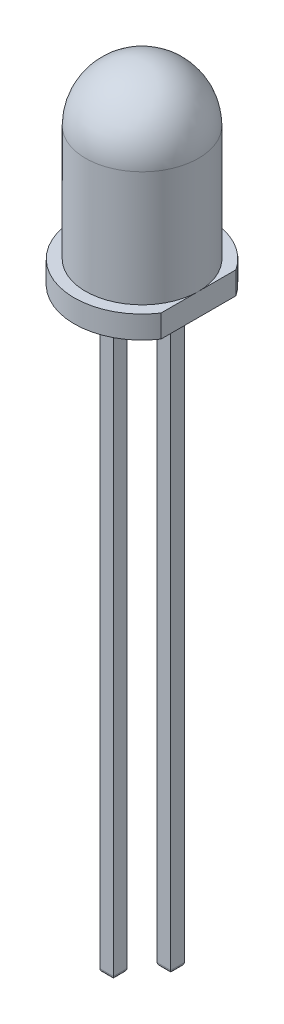
SolidWorks part; units mm, degrees
ref_plane "Front Plane" through (0, 0, 0) normal (0, 0, 1) x (1, 0, 0)
ref_plane "Top Plane" through (0, 0, 0) normal (0, 1, 0) x (1, 0, 0)
ref_plane "Right Plane" through (0, 0, 0) normal (1, 0, 0) x (0, 0, -1)
sketch "Sketch1" plane through (0, 0, 0) normal (0, 1, 0) x (1, 0, 0)
  circle A0 centre (0, 0) radius 2.5
  dimension "D1" = 5
extrude "Boss-Extrude1" add sketch "Sketch1" along normal mid plane 8.6
sketch "Sketch2" plane through (0, -4.3, 0) normal (0, -1, 0) x (1, 0, 0)
  circle A0 centre (0, 0) radius 3
  dimension "D1" = 6
extrude "Boss-Extrude2" add sketch "Sketch2" against normal blind 1
fillet "Fillet1" radius 2.5 1 edges at (0, 4.3, 2.5)
sketch "Sketch3" plane through (0, 0, 0) normal (0, 0, 1) x (1, 0, 0)
  line L1 (2.5, -3.3) -> (3.4542, -3.3)
  line L2 (2.5, -3.3) -> (2.5, -4.7256)
  line L3 (2.5, -4.7256) -> (3.4542, -4.7256)
  line L4 (3.4542, -3.3) -> (3.4542, -4.7256)
extrude "Cut-Extrude1" cut sketch "Sketch3" against normal through all both and the other way through all
sketch "Sketch4" plane through (0, -4.3, 0) normal (0, -1, 0) x (1, 0, 0)
  line L1 (-0.97, -0.3) -> (-1.57, -0.3)
  line L2 (-0.97, -0.3) -> (-0.97, 0.3)
  line L3 (-0.97, 0.3) -> (-1.57, 0.3)
  line L4 (-1.57, -0.3) -> (-1.57, 0.3)
  line L5 (-0.97, -0.3) -> (-1.57, 0.3) construction
  line L6 (-0.97, 0.3) -> (-1.57, -0.3) construction
  line L7 (0.97, 0.3) -> (1.57, 0.3)
  line L8 (0.97, 0.3) -> (0.97, -0.3)
  line L9 (0.97, -0.3) -> (1.57, -0.3)
  line L10 (1.57, 0.3) -> (1.57, -0.3)
  line L11 (0.97, 0.3) -> (1.57, -0.3) construction
  line L12 (0.97, -0.3) -> (1.57, 0.3) construction
  point P0 (-1.27, 0)
  point P5 (1.27, 0)
  dimension "D1" = 0.3
  dimension "D2" = 0.6
  dimension "D3" = 0.6
  dimension "D4" = 0.3
  dimension "D5" = 2.54
  dimension "D6" = 1.27
extrude "Boss-Extrude3" add sketch "Sketch4" along normal blind 27 contours L2 L3 L4 L1
extrude "Boss-Extrude4" add sketch "Sketch4<3>" along normal blind 25.5 contours L7 L10 L9 L8
sketch "Sketch4<3>" plane through (0, -4.3, 0) normal (0, -1, 0) x (1, 0, 0) same geometry as "Sketch4"
fillet "Fillet2" radius 0.15 4 edges at (-1.57, -4.3, 0) (-1.27, -4.3, -0.3) (-0.97, -4.3, 0) (-1.27, -4.3, 0.3)
fillet "Fillet3" radius 0.15 4 edges at (1.27, -4.3, -0.3) (1.57, -4.3, 0) (0.97, -4.3, 0) (1.27, -4.3, 0.3)
fillet "Fillet4" radius 0.15 4 edges at (-1.57, -31.3, 0) (-1.27, -31.3, 0.3) (-0.97, -31.3, 0) (-1.27, -31.3, -0.3)
fillet "Fillet5" radius 0.15 4 edges at (1.27, -29.8, 0.3) (1.57, -29.8, 0) (1.27, -29.8, -0.3) (0.97, -29.8, 0)
